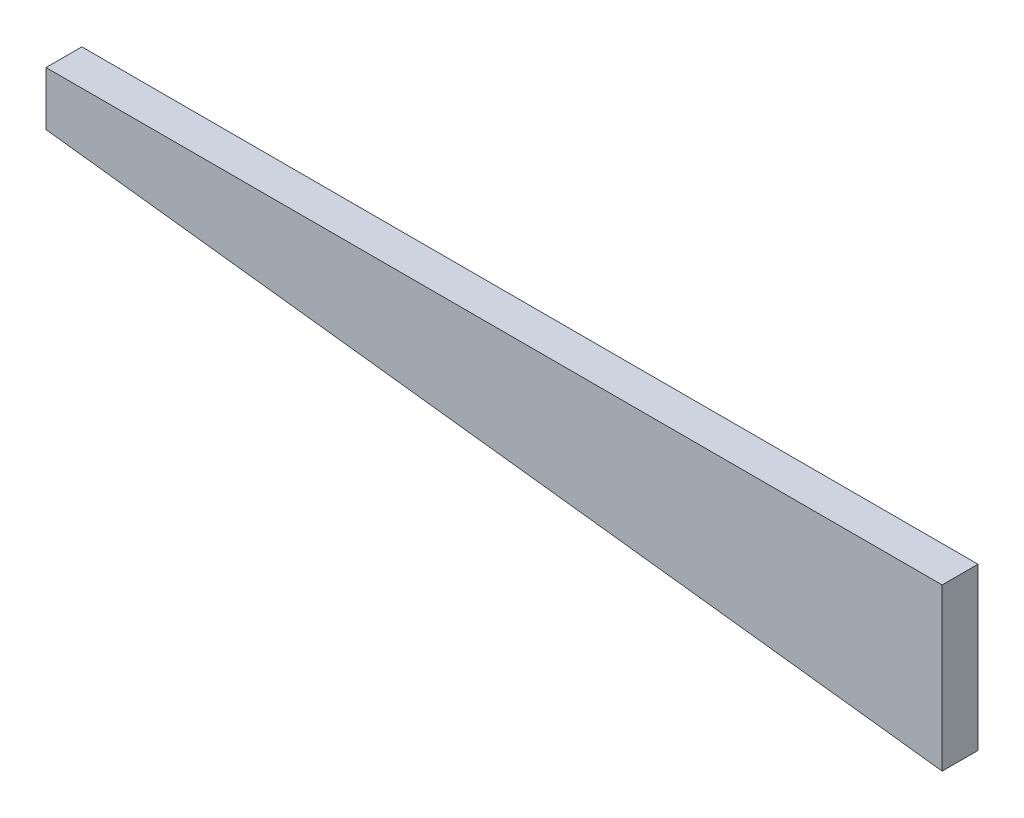
SolidWorks part; units mm, degrees
ref_plane "Front Plane" through (0, 0, 0) normal (0, 0, 1) x (1, 0, 0)
ref_plane "Top Plane" through (0, 0, 0) normal (0, 1, 0) x (1, 0, 0)
ref_plane "Right Plane" through (0, 0, 0) normal (1, 0, 0) x (0, 0, -1)
other "Configuration Table"
sketch "Sketch1" plane through (0, 0, 0) normal (0, 0, 1) x (1, 0, 0)
  line L0 (-81.3443, 14.5398) -> (-1351.3443, 14.5398)
  line L1 (-1351.3443, 14.5398) -> (-1351.3443, -61.6602)
  line L2 (-81.3443, 14.5398) -> (-81.3443, -214.0602)
  line L3 (-1351.3443, -61.6602) -> (-81.3443, -214.0602)
sheet metal parameters "Sheet-Metal1" thickness 50.8 parameters "D1"=0.7366
base flange "Base-Flange1" sketch "Sketch1" thickness 50.8 reverse thickness direction yes parameters "D1"=0.7366
flat pattern "Flat-Pattern1" [suppressed]
sketch "Bend-Lines1" plane through (0, 0, 0) normal (0, 1, 0) x (-1, 0, 0)
